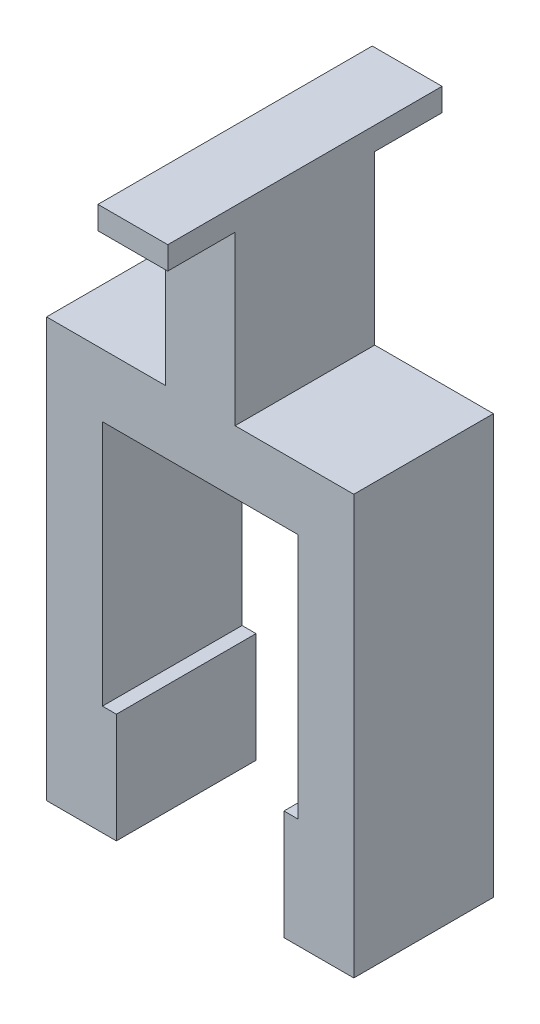
SolidWorks part; units mm, degrees
ref_plane "前视基准面" through (0, 0, 0) normal (0, 0, 1) x (1, 0, 0)
ref_plane "上视基准面" through (0, 0, 0) normal (0, 1, 0) x (1, 0, 0)
ref_plane "右视基准面" through (0, 0, 0) normal (1, 0, 0) x (0, 0, -1)
sketch "草图1" plane through (0, 0, 0) normal (0, 0, 1) x (1, 0, 0)
  line L0 (-6, -2.7154) -> (-6, -10.5746)
  line L1 (-6, -10.5746) -> (-11, -10.5746)
  line L2 (-11, -10.5746) -> (-11, 19.4254)
  line L3 (-11, 19.4254) -> (-5, 19.4254)
  line L4 (-5, 19.4254) -> (-5, 31.4254) construction
  line L5 (-5, 31.4254) -> (-12.0747, 31.4254) construction
  line L6 (-12.0747, 31.4254) -> (-12.0747, 35.4254) construction
  line L7 (-12.0747, 35.4254) -> (12.0747, 35.4254) construction
  line L8 (0, 35.4254) -> (0, 14.9254) construction
  line L9 (7, 14.9254) -> (-7, 14.9254)
  line L10 (-7, 14.9254) -> (-7, -2.7154)
  line L11 (-7, -2.7154) -> (-6, -2.7154)
  line L12 (0, 33.9868) -> (0, 35.4254) construction
  line L13 (7, 14.9254) -> (7, -2.7154)
  line L14 (12.0747, 31.4254) -> (12.0747, 35.4254) construction
  line L15 (5, 31.4254) -> (12.0747, 31.4254) construction
  line L16 (5, 19.4254) -> (5, 31.4254) construction
  line L17 (11, 19.4254) -> (5, 19.4254)
  line L18 (11, -10.5746) -> (11, 19.4254)
  line L19 (6, -10.5746) -> (11, -10.5746)
  line L20 (6, -2.7154) -> (6, -10.5746)
  line L21 (7, -2.7154) -> (6, -2.7154)
  line L22 (0, 35.4254) -> (0, 14.9254) construction
  line L23 (0, 14.9254) -> (0, -23.5296) construction
  line L24 (-5, 19.4254) -> (5, 19.4254)
  dimension "D1" = 12
  dimension "D2" = 5
  dimension "D3" = 14
  dimension "D4" = 10
  dimension "D5" = 4
  dimension "D6" = 30
  dimension "D7" = 4.5
  dimension "D8" = 12
extrude "凸台-拉伸1" add sketch "草图1" along normal blind 10
sketch "草图2" plane through (0, 0, 0) normal (1, 0, 0) x (0, 0, -1)
  line L0 (-10, 19.4254) -> (-10, 31.4254)
  line L1 (-10, 31.4254) -> (-14.8212, 31.4254)
  line L2 (-14.8212, 31.4254) -> (-14.8212, 33.0637)
  line L3 (-14.8212, 33.0637) -> (4.8212, 33.0637)
  line L4 (-5, 33.0637) -> (-5, 19.4254) construction
  line L5 (-10, 19.4254) -> (0, 19.4254) construction
  line L6 (0, 19.4254) -> (-10, 19.4254)
  line L7 (-5, 12.2924) -> (-5, 19.4254) construction
  line L8 (4.8212, 31.4254) -> (4.8212, 33.0637)
  line L9 (0, 31.4254) -> (4.8212, 31.4254)
  line L10 (0, 19.4254) -> (0, 31.4254)
  line L11 (-5, 19.4254) -> (-5, 33.0637) construction
  line L12 (-5, 33.0637) -> (-5, 21.1812) construction
  dimension "D1" = 12
  dimension "D2" = 4.8212
extrude "凸台-拉伸2" add sketch "草图2" along normal blind 2.5
extrude "凸台-拉伸3" add sketch "草图2<2>" against normal blind 2.5
sketch "草图2<2>" plane through (0, 0, 0) normal (1, 0, 0) x (0, 0, -1) same geometry as "草图2"
